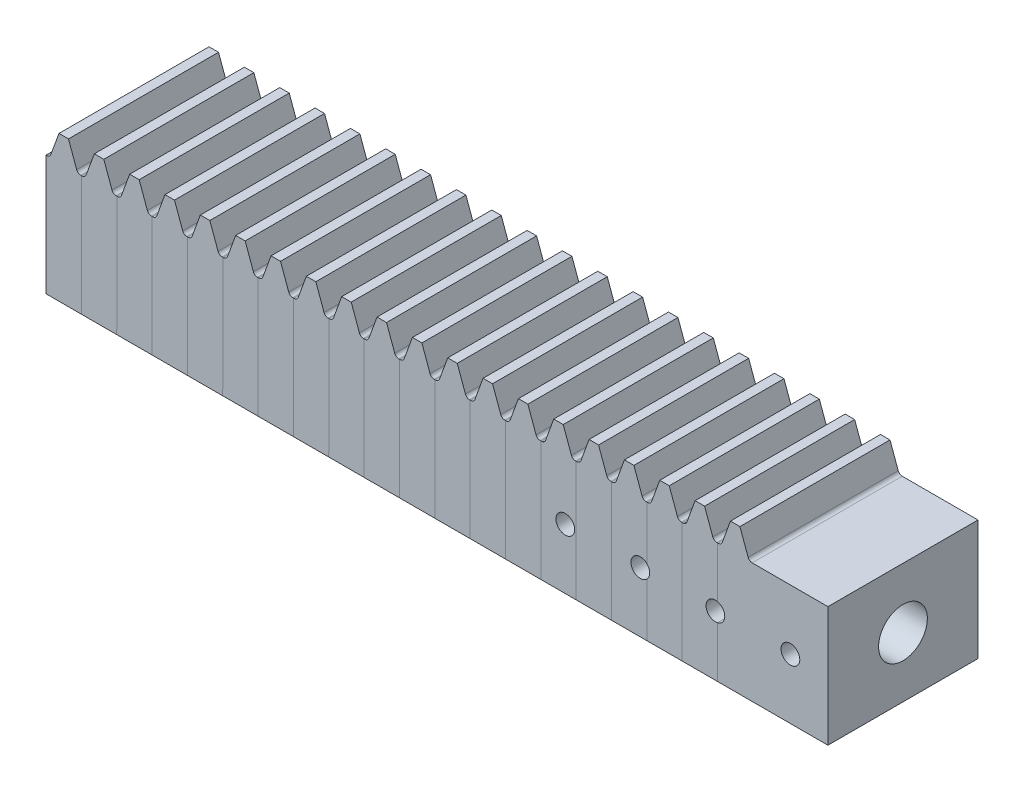
SolidWorks part; units mm, degrees
note: '?' marks a value the reader was unsure of.
ref_plane "Front Plane" through (0, 0, 0) normal (0, 0, 1) x (1, 0, 0)
ref_plane "Top Plane" through (0, 0, 0) normal (0, 1, 0) x (1, 0, 0)
ref_plane "Right Plane" through (0, 0, 0) normal (1, 0, 0) x (0, 0, -1)
ref_axis "Axis1" through (0.1856, 0, 0) along (-1, 0, 0)?
sketch "Sketch1" plane through (0, 0, 0) normal (0, 0, 1) x (1, 0, 0)
  line L0 (-3.7211, 0) -> (-2.4927, 3.375)
  line L1 (-2.4927, 3.375) -> (-1.2284, 3.375)
  line L2 (-1.2284, 3.375) -> (0, 0)
  line L3 (-3.7211, 0) -> (-4.7124, 0) construction
  line L4 (-3.7211, 0) -> (0, 0)
  line L5 (-3.5846, 0.375) -> (-4.8489, 0.375) construction
  line L6 (-4.7124, 0) -> (-5.3948, 1.875) construction
  line L7 (-5.3948, 1.875) -> (-0.6824, 1.875) construction
  dimension "D1" = 1.5
  dimension "D2" = 3.375
  dimension "D3" = 4.7124
  dimension "D4" = 3
  dimension "D5" = 70
  dimension "D6" = 0.9913
extrude "Main" add sketch "Sketch1" along normal blind 20
sketch "Sketch2" plane through (0, 0, 20) normal (0, 0, 1) x (1, 0, 0)
  line L1 (-4.2211, 0) -> (0.5, 0)
  line L2 (-4.2211, 0) -> (-4.2211, -16)
  line L3 (-4.2211, -16) -> (0.5, -16)
  line L4 (0.5, 0) -> (0.5, -16)
  line L6 (0.1856, 0) -> (-3.898, 0) construction
  point P12 (0, 0)
  dimension "D1" = 16
  dimension "D2" = 0.5
  dimension "D3" = 0.5
extrude "Support" add sketch "Sketch2" against normal up to surface (20 mm away) up to face at (-1.8605, 1.6875, 0)
sketch "Sketch3" plane through (-4.2211, 0, 0) normal (-1, 0, 0) x (0, 0, 1)
  line L0 (0, -16) -> (20, -16) construction
  line L1 (20, 0) -> (20, -16) construction
  circle A0 centre (10, -8) radius 6.15
  point P2 (10, -16)
  point P3 (20, -8)
  dimension "D1" = 12.3
extrude "AxisHole" cut sketch "Sketch3" against normal through all
fillet "Fillet1" radius 0.57 2 edges at (-3.7211, 0, 10) (0, 0, 10)
pattern_linear "LPattern2" count 20 spacing 4.71 along (-1, 0, 0) of bodies 112
sketch "Sketch4" plane through (0.5, 0, 0) normal (1, 0, 0) x (0, 0, -1)
  line L0 (0, -16) -> (-20, -16) construction
  line L1 (-20, -16) -> (0, -16)
  line L2 (-20, -16) -> (-20, 0)
  line L3 (-20, 0) -> (0, 0)
  line L4 (0, -16) -> (0, 0)
  line L5 (-20, 0) -> (0, 0) construction
  line L6 (0, 0) -> (-20, 0) construction
  circle A0 centre (-10, -8) radius 3.25
  circle A1 centre (-10, -8) radius 6.15 construction
  point P14 (-10, 0)
  dimension "D1" = 6.5
  dimension "D2" = 20
extrude "Boss-Extrude1" add sketch "Sketch4" along normal blind 10
sketch "Sketch5" plane through (0, 0, 20) normal (0, 0, 1) x (1, 0, 0)
  line L0 (10.5, -16) -> (-4.2211, -16) construction
  line L1 (10.5, 0) -> (10.5, -16) construction
  circle A0 centre (5.5, -8) radius 1.25
  dimension "D1" = 8
  dimension "D2" = 2.5
  dimension "D3" = 5
extrude "Cut-Extrude1" cut sketch "Sketch5" against normal through all
pattern_linear "LPattern3" count 4 spacing 10 along (-1, 0, 0) of "Cut-Extrude1"
